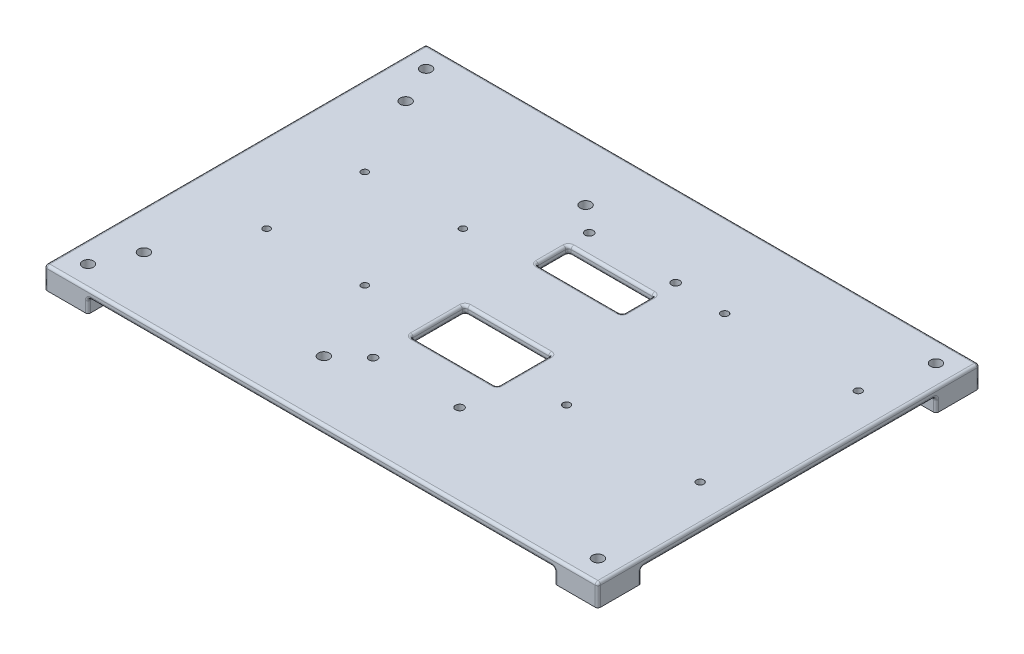
SolidWorks part; units mm, degrees
ref_plane "前视基准面" through (0, 0, 0) normal (0, 0, 1) x (1, 0, 0)
ref_plane "上视基准面" through (0, 0, 0) normal (0, 1, 0) x (1, 0, 0)
ref_plane "右视基准面" through (0, 0, 0) normal (1, 0, 0) x (0, 0, -1)
sketch "草图1" plane through (0, 0, 0) normal (0, 1, 0) x (1, 0, 0)
  line L0 (53, 0) -> (53, 79) construction
  line L1 (50, 82) -> (0, 82) construction
  line L2 (-3, 79) -> (-3, 0) construction
  line L3 (0, -3) -> (50, -3) construction
  line L4 (-5, -2.825) -> (-53, -2.825) construction
  line L5 (-53, -2.825) -> (-53, 81.825) construction
  line L6 (-53, 81.825) -> (-5, 81.825) construction
  line L7 (-5, 81.825) -> (-5, -2.825) construction
  line L8 (-3, 39.5) -> (-5, 39.5) construction
  line L9 (-57, 92) -> (-128, 92) construction
  line L10 (-130, 90) -> (-130, -11) construction
  line L11 (-128, -13) -> (-57, -13) construction
  line L12 (-55, -11) -> (-55, 90) construction
  line L13 (-53, 39.5) -> (-55, 39.5) construction
  line L14 (101.3098, 39.5) -> (-319.8116, 39.5) construction
  line L15 (-130, 39.5) -> (-140, 39.5) construction
  line L16 (-140, 39.5) -> (-140, 109.5)
  line L17 (53, 39.5) -> (63, 39.5) construction
  line L18 (63, 39.5) -> (63, 109.5)
  line L19 (63, 109.5) -> (-140, 109.5)
  line L20 (-140, 39.5) -> (-140, -30.5)
  line L21 (-140, -30.5) -> (63, -30.5)
  line L22 (63, -30.5) -> (63, 39.5)
  line L23 (-140, 109.5) -> (-132, 109.5)
  line L24 (-132, 109.5) -> (-132, 101.5) construction
  line L25 (-132, -30.5) -> (-132, -22.5) construction
  line L26 (63, 101.5) -> (55, 101.5) construction
  circle A0 centre (49.5, 78.5) radius 1.35
  arc A1 (50, -3) -> (53, 0) centre (50, 0) ccw construction
  arc A2 (53, 79) -> (50, 82) centre (50, 79) ccw construction
  arc A3 (0, 82) -> (-3, 79) centre (0, 79) ccw construction
  arc A4 (-3, 0) -> (0, -3) centre (0, 0) ccw construction
  circle A5 centre (49.5, 20.5) radius 1.35
  circle A6 centre (0.5, 20.5) radius 1.35
  circle A7 centre (0.5, 78.5) radius 1.35
  circle A8 centre (-50, 0.075) radius 1.5
  circle A9 centre (-18.3, 0.075) radius 1.5
  circle A10 centre (-50, 79.325) radius 1.5
  circle A11 centre (-18.3, 79.325) radius 1.5
  arc A12 (-128, 92) -> (-130, 90) centre (-128, 90) ccw construction
  arc A13 (-130, -11) -> (-128, -13) centre (-128, -11) ccw construction
  arc A14 (-57, -13) -> (-55, -11) centre (-57, -11) ccw construction
  arc A15 (-55, 90) -> (-57, 92) centre (-57, 90) ccw construction
  circle A16 centre (-59.5, -8.5) radius 2
  circle A17 centre (-125.5, -8.5) radius 2
  circle A18 centre (-125.5, 87.5) radius 2
  circle A19 centre (-59.5, 87.5) radius 2
  circle A20 centre (-132, 101.5) radius 2
  circle A21 centre (-132, -22.5) radius 2
  circle A22 centre (55, 101.5) radius 2
  circle A23 centre (55, -22.5) radius 2
  dimension "D1" = 48
extrude "凸台-拉伸1" add sketch "草图1" along normal blind 3 contours L21 L22 L18 L19 L16 L20 A23 A22 A21 A20 A19 A18 A17 A16 A11 A10 A9 A8 A7 A6 A5 A0 region at (-38.4598, 0, -39.4917)
sketch "草图2" plane through (0, 3, 0) normal (0, 1, 0) x (1, 0, 0)
  line L16 (-50, 79.325) -> (-18.3, 79.325) construction
  line L17 (-18.3, 79.325) -> (-18.3, 0.075) construction
  line L18 (-18.3, 0.075) -> (-50, 0.075) construction
  line L20 (-50, 39.7) -> (-50, 59.7) construction
  line L21 (-50, 33.7982) -> (-50, 13.7982)
  line L22 (-50, 59.7) -> (-18.3, 59.7)
  line L23 (-18.3, 59.7) -> (-18.3, 71.7)
  line L24 (-18.3, 71.7) -> (-50, 71.7)
  line L25 (-50, 71.7) -> (-50, 59.7)
  line L32 (-50, 33.7982) -> (-18.3, 33.7982)
  line L34 (-50, 13.7982) -> (-18.3, 13.7982)
  line L35 (-18.3, 33.7982) -> (-18.3, 13.7982)
extrude "切除-拉伸3" cut sketch "草图2" against normal blind 10
fillet "圆角3" radius 1 24 edges at (-34.15, 0, -13.7982) (-34.15, 3, -13.7982) (-18.3, 0, -23.7982) (-18.3, 3, -23.7982) (-18.3, 1.5, -13.7982) (-50, 0, -23.7982) (-50, 1.5, -13.7982) (-50, 3, -23.7982) (-34.15, 0, -33.7982) (-50, 1.5, -33.7982) (-34.15, 3, -33.7982) (-18.3, 1.5, -33.7982) (-34.15, 0, -59.7) (-34.15, 3, -59.7) (-18.3, 0, -65.7) (-18.3, 3, -65.7) (-18.3, 1.5, -59.7) (-34.15, 0, -71.7) (-34.15, 3, -71.7) (-18.3, 1.5, -71.7) (-50, 0, -65.7) (-50, 1.5, -59.7) (-50, 3, -65.7) (-50, 1.5, -71.7)
sketch "草图3" plane through (0, 0, 0) normal (0, -1, 0) x (1, 0, 0)
  line L0 (-140, -109.5) -> (-140, -93.5)
  line L1 (-140, -93.5) -> (-124, -93.5)
  line L2 (-124, -93.5) -> (-124, -109.5)
  line L3 (-140, 30.5) -> (-140, 14.5)
  line L4 (63, 30.5) -> (-140, 30.5)
  line L5 (-140, 30.5) -> (-140, -109.5)
  line L6 (-140, -109.5) -> (63, -109.5)
  line L7 (63, -109.5) -> (63, 30.5)
  line L8 (63, 30.5) -> (47, 30.5)
  line L10 (-140, -109.5) -> (-124, -109.5)
  line L11 (63, -109.5) -> (63, -93.5)
  line L12 (-140, 14.5) -> (-124, 14.5)
  line L13 (-124, 14.5) -> (-124, 30.5)
  line L14 (63, -109.5) -> (47, -109.5)
  line L15 (47, -109.5) -> (47, -93.5)
  line L16 (47, -93.5) -> (63, -93.5)
  line L17 (47, 30.5) -> (47, 14.5)
  line L18 (47, 14.5) -> (63, 14.5)
  line L19 (47, -109.5) -> (63, -109.5)
  line L20 (63, 14.5) -> (63, 30.5)
  line L21 (-124, 30.5) -> (-140, 30.5)
  circle A0 centre (55, 22.5) radius 2 construction
  circle A1 centre (55, -101.5) radius 2 construction
  circle A2 centre (-132, 22.5) radius 2 construction
  circle A3 centre (-132, -101.5) radius 2 construction
  circle A4 centre (55, 22.5) radius 2
  circle A5 centre (55, -101.5) radius 2
  circle A6 centre (-132, 22.5) radius 2
  circle A7 centre (-132, -101.5) radius 2
  line M5 (63, 30.5) -> (-140, 30.5)
  line M6 (-140, 30.5) -> (-140, -109.5)
  line M7 (-140, -109.5) -> (63, -109.5)
  line M8 (63, -109.5) -> (63, 30.5)
  circle M21 centre (-132, -101.5) radius 2
  circle M22 centre (-132, 22.5) radius 2
  circle M23 centre (55, -101.5) radius 2
  circle M24 centre (55, 22.5) radius 2
  dimension "D1" = 0
extrude "凸台-拉伸2" add sketch "草图3" along normal blind 5 contours L2 L1 M6 M7 M21 | L12 L13 M5 M6 M22 | L16 L15 M7 M8 M23 | L17 L18 M8 M5 M24 region at (-139.7737, 0, -101.5) region at (-139.7737, 0, 22.5) region at (47.2263, 0, -101.5) region at (55, 0, 30.2737)
fillet "圆角4" radius 1 32 edges at (-140, -2.5, -93.5) (-140, 0, -39.5) (-124, 0, -101.5) (-132, 0, 14.5) (-38.5, 0, 30.5) (47, 0, 22.5) (63, 0, -39.5) (-38.5, 3, -109.5) (-140, 3, -39.5) (-140, -1, -109.5) (-132, 0, -93.5) (-124, -2.5, -93.5) (-124, -2.5, -109.5) (-124, -2.5, 14.5) (-124, 0, 22.5) (-140, -2.5, 14.5) (-124, -2.5, 30.5) (-140, -1, 30.5) (47, -2.5, 30.5) (47, -2.5, 14.5) (55, 0, 14.5) (63, -2.5, 14.5) (63, -1, 30.5) (-38.5, 3, 30.5) (63, 3, -39.5) (55, 0, -93.5) (63, -2.5, -93.5) (47, -2.5, -93.5) (47, 0, -101.5) (47, -2.5, -109.5) (-38.5, 0, -109.5) (63, -1, -109.5)
sketch "草图4" plane through (0, 3, 0) normal (0, 1, 0) x (1, 0, 0)
  line L0 (-74.5, 57.5) -> (-110.5, 21.5) construction
  line L1 (-110.5, 57.5) -> (-74.5, 21.5) construction
  line L2 (-59.5, 87.5) -> (-125.5, -8.5) construction
  line L3 (-59.5, -8.5) -> (-125.5, 87.5) construction
  arc A0 (-109.25, 21.5) -> (-111.75, 21.5) centre (-110.5, 21.5) ccw
  arc A1 (-111.75, 21.5) -> (-109.25, 21.5) centre (-110.5, 21.5) ccw
  arc A2 (-73.25, 21.5) -> (-75.75, 21.5) centre (-74.5, 21.5) ccw
  arc A3 (-75.75, 21.5) -> (-73.25, 21.5) centre (-74.5, 21.5) ccw
  arc A4 (-73.25, 57.5) -> (-75.75, 57.5) centre (-74.5, 57.5) ccw
  arc A5 (-75.75, 57.5) -> (-73.25, 57.5) centre (-74.5, 57.5) ccw
  arc A6 (-109.25, 57.5) -> (-111.75, 57.5) centre (-110.5, 57.5) ccw
  arc A7 (-111.75, 57.5) -> (-109.25, 57.5) centre (-110.5, 57.5) ccw
  circle A8 centre (-125.5, 87.5) radius 2 construction
  circle A9 centre (-125.5, -8.5) radius 2 construction
  circle A10 centre (-59.5, -8.5) radius 2 construction
  circle A11 centre (-59.5, 87.5) radius 2 construction
  circle A12 centre (-125.5, 87.5) radius 2 construction
  circle A13 centre (-125.5, -8.5) radius 2 construction
  circle A14 centre (-59.5, -8.5) radius 2
  circle A15 centre (-59.5, 87.5) radius 2 construction
extrude "切除-拉伸4" cut sketch "草图4" against normal blind 10
